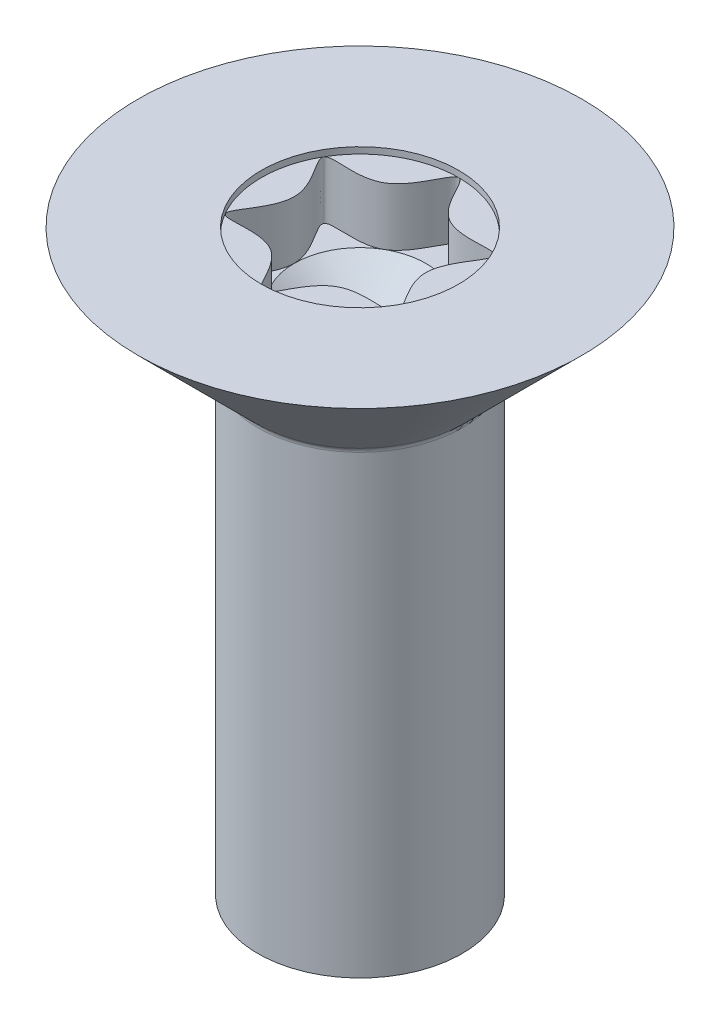
SolidWorks part; units mm, degrees
ref_plane "Front" through (0, 0, 0) normal (0, 0, 1) x (1, 0, 0)
ref_plane "Top" through (0, 0, 0) normal (0, 1, 0) x (1, 0, 0)
ref_plane "Right" through (0, 0, 0) normal (1, 0, 0) x (0, 0, -1)
sketch "Sketch1" plane through (0, 0, 0) normal (0, 0, 1) x (1, 0, 0)
  line L0 (0, 0) -> (0, 8.8882) construction
  line L1 (0, 8.2) -> (3.15, 8.2)
  line L2 (1.45, 0) -> (1.45, 6.5)
  line L3 (1.45, 6.5) -> (2.55, 6.5) construction
  line L4 (2.55, 6.5) -> (2.55, 5.4) construction
  line L5 (1.45, 0) -> (0, 0)
  line L6 (0, 0) -> (0, 8.2)
  line L7 (3.15, 8.2) -> (1.45, 6.5)
  dimension "head_ht" = 1.7
  dimension "D1" = 45
revolve "Body-Revolve" add sketch "Sketch1" angle 360 about L0
cosmetic thread "ThreadCosmetic" [suppressed] parameters "D1"=5.4, "D2"=1.7092
sketch "Sketch2" plane through (0, 8.2, 0) normal (0, 1, 0) x (-1, 0, 0)
  line L0 (0, 0) -> (0, -1.54)
  line L1 (0, 0) -> (-0.7, -1.2124)
  circle A0 centre (0, 0) radius 1.4
  circle A1 centre (0, 0) radius 0.9333
  spline S0 degree 3 poles (0.302, -0.523) (0, -1.8385) (-0.302, -0.523) (-1.5922, -0.9193) (-0.6039, 0) (-1.5922, 0.9193) (-0.302, 0.523) (0, 1.8385) (0.302, 0.523) (1.5922, 0.9193) (0.6039, 0) (1.5922, -0.9193) (0.302, -0.523) (0, -1.8385) (-0.302, -0.523) knots -0.25 -0.166667 -0.083333 0 0.083333 0.166667 0.25 0.333333 0.416667 0.5 0.583333 0.666667 0.75 0.833333 0.916667 1 1.083333 1.166667 1.25 only from (0, -1.4) to (0, -1.4)
  point P4 (0, -1.4)
  point P7 (-0.4667, -0.8083)
  point P10 (-1.2124, -0.7)
  point P11 (-1.2124, 0.7)
  point P12 (0, 1.4)
  point P13 (1.2124, 0.7)
  point P14 (1.2124, -0.7)
  point P15 (-0.9333, 0)
  point P16 (-0.4667, 0.8083)
  point P17 (0.4667, 0.8083)
  point P18 (0.9333, 0)
  point P19 (0.4667, -0.8083)
  dimension "D1" = 1.8667
  dimension "D2" = 30
  dimension "D3" = 1.54
extrude "Recess-Cut-Extrude1" cut sketch "Sketch2" against normal blind 0.91 contours S0
sketch "Sketch3" plane through (0, 8.2, 0) normal (0, 1, 0) x (-1, 0, 0)
  circle A0 centre (0, 0) radius 1.4
  dimension "D1" = 2.8
extrude "Recess-Cut-Extrude2" cut sketch "Sketch3" against normal blind 0.091
sketch "Sketch4" plane through (0, 0, 0) normal (0, 0, 1) x (1, 0, 0)
  line L0 (0, 7.29) -> (0.9333, 7.29)
  line L1 (1.2177, 7.29) -> (-1.2177, 7.29) construction
  line L2 (0.9333, 7.29) -> (0, 6.67)
  line L3 (0, 0) -> (0, 8.8882) construction
  line L4 (0, 6.67) -> (0, 7.29)
  line L5 (1.4, 8.2) -> (-1.4, 8.2) construction
  dimension "D1" = 1.53
  dimension "D2" = 0.9333
revolve "Drill-Cut-Revolve" cut sketch "Sketch4" angle 360 about axis through (0, 0, 0) along (0, 1, 0)
fillet "Fillet1" radius 0.1 1 edges at (0, 6.5, -1.45)
sketch "Sketch5" plane through (0, 0, 0) normal (0, 0, 1) x (1, 0, 0)
  line L0 (1.45, 5.4) -> (1.45, 4.7125)
  line L1 (1.45, 0) -> (1.45, 6.4586) construction
  line L2 (1.45, 4.7125) -> (0.8546, 5.0563)
  line L3 (0.8546, 5.0563) -> (1.45, 5.4)
  line L4 (0, 0) -> (0, 8.8882) construction
  line L5 (-1.45, 0) -> (1.45, 0) construction
  dimension "D1" = 0.8546
  dimension "D2" = 5.4
revolve "ThreadSchematic" [suppressed] cut sketch "Sketch5" angle 360 about axis through (0, 0, 0) along (0, 1, 0)
pattern_linear "ThdSchPat" [suppressed] count 5 spacing 1.1 along (0, -1, 0) of bodies 105
sketch "Sketch6" plane through (0, 0, 0) normal (0, 0, 1) x (1, 0, 0)
  line L0 (0.01, 0) -> (1.45, 0)
  line L1 (-1.45, 0) -> (1.45, 0) construction
  line L2 (1.45, 0) -> (1.45, 2.6)
  line L4 (1.45, 2.6) -> (0.01, 0)
  line L5 (0, 0) -> (0, 8.8882) construction
  dimension "D1" = 1.45
  dimension "D2" = 0.01
revolve "TypeC" [suppressed] cut sketch "Sketch6" angle 360 about axis through (0, 0, 0) along (0, 1, 0)
sketch "Sketch7" plane through (0, 0, 0) normal (0, 0, 1) x (1, 0, 0)
  line L0 (1.2293, 0) -> (1.45, 0)
  line L1 (0, 0) -> (0, 8.8882) construction
  line L2 (1.45, 0) -> (1.45, 2.1)
  line L4 (1.45, 2.1) -> (1.2293, 0)
  line L5 (-1.45, 0) -> (1.45, 0) construction
  dimension "D1" = 6
  dimension "D2" = 1.45
revolve "TypeF" [suppressed] cut sketch "Sketch7" angle 360 about axis through (0, 0, 0) along (0, 1, 0)
sketch "Sketch8" plane through (0, 0, 0) normal (0, 0, 1) x (1, 0, 0)
  line L0 (1.45, -0.09) -> (1.45, 2)
  line L2 (1.45, 2) -> (0.1163, 0.0456)
  line L3 (0.03, 0) -> (0.03, -0.09)
  line L4 (0.03, -0.09) -> (1.45, -0.09)
  line L5 (0, 0) -> (0, 8.8882) construction
  line L9 (-1.45, 0) -> (1.45, 0) construction
  arc A0 (0.1163, 0.0456) -> (0.03, 0) centre (0.03, 0.1045) cw
  dimension "D4" = 0.1045
  dimension "D1" = 0.09
  dimension "D2" = 0.03
  dimension "D3" = 1.45
revolve "TypeR" [suppressed] cut sketch "Sketch8" angle 360 about axis through (0, 0, 0) along (0, 1, 0)
equation "\"thread_gap@Sketch1\" = \"pitch@Sketch1\""
equation "\"D1@ThreadCosmetic\" = \"length@Sketch1\" - \"head_ht@Sketch1\" - \"thread_gap@Sketch1\""
equation "\"D2@ThreadCosmetic\" = \"head_dia@Sketch1\" - \"head_ht@Sketch1\" * 2 - 1.0825 * \"pitch@Sketch1\""
equation "\"D1@Sketch2\" = \"socket_dia@Sketch2\" / 1.5"
equation "\"D3@Sketch2\" = \"socket_dia@Sketch2\" / 2 * 1.1"
equation "\"D1@Sketch3\" = \"socket_dia@Sketch2\""
equation "\"D1@Recess-Cut-Extrude2\" = 0.1 * \"socket-dep@Recess-Cut-Extrude1\""
equation "\"D1@Sketch4\" = 0.9*\"head_ht@Sketch1\""
equation "\"D2@Sketch4\" = \"D1@Sketch2\" / 2"
equation "\"D1@Sketch5\" = \"D2@ThreadCosmetic\" / 2"
equation "\"D2@Sketch5\" = \"D1@ThreadCosmetic\""
equation "\"D3@ThdSchPat\" = \"pitch@Sketch1\""
equation "\"D1@ThdSchPat\" = \"D1@ThreadCosmetic\" / \"D3@ThdSchPat\""
equation "\"D1@Sketch6\" = \"head_dia@Sketch1\" / 2 - \"head_ht@Sketch1\""
equation "\"D2@Sketch7\" = \"head_dia@Sketch1\" / 2 - \"head_ht@Sketch1\""
equation "\"D3@Sketch8\" = \"head_dia@Sketch1\" * 0.5 - \"head_ht@Sketch1\""
equation "\"D4@Sketch8\" = \"end_lengthR@Sketch8\" / 20"
